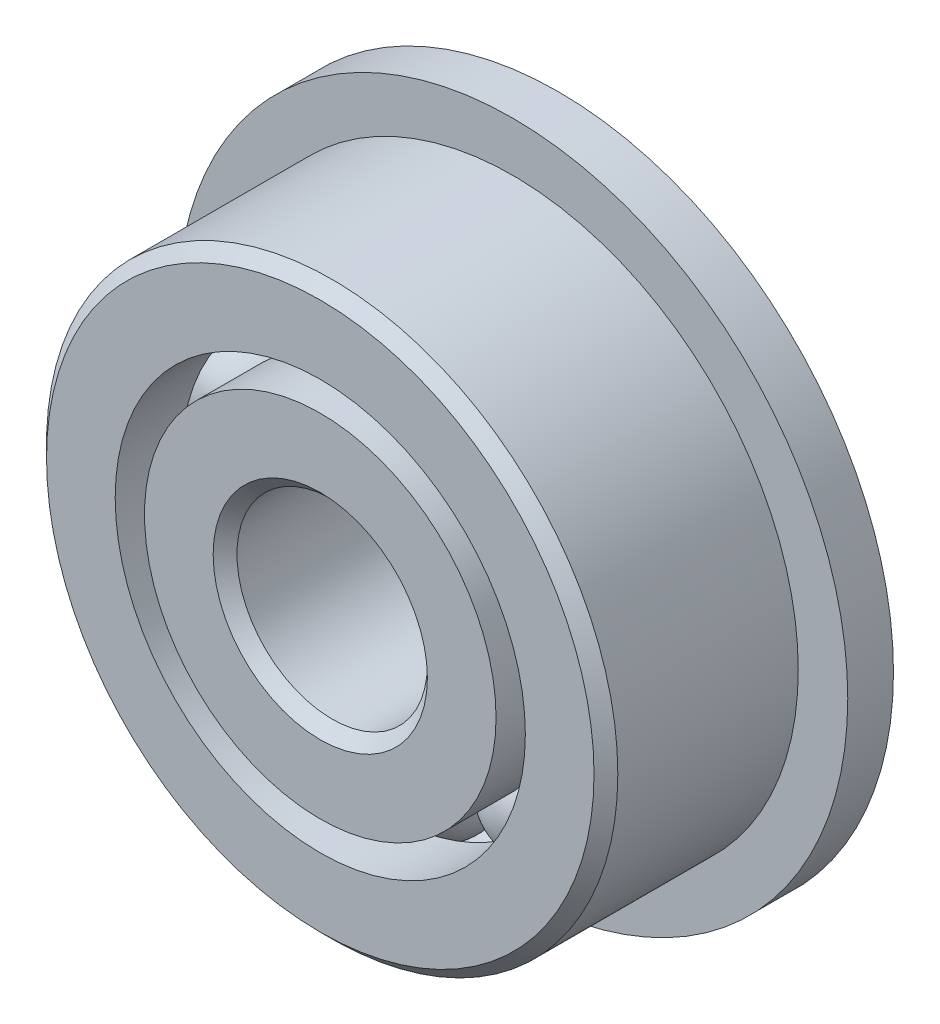
SolidWorks part; units mm, degrees
ref_plane "Front Plane" through (0, 0, 0) normal (0, 0, 1) x (1, 0, 0)
ref_plane "Top Plane" through (0, 0, 0) normal (0, 1, 0) x (1, 0, 0)
ref_plane "Right Plane" through (0, 0, 0) normal (1, 0, 0) x (0, 0, -1)
sketch "Sketch1" plane through (0, 0, 0) normal (1, 0, 0) x (0, 0, -1)
  line L0 (-1.9844, 0) -> (1.9844, 0) construction
  line L1 (0, 4.7625) -> (0, -4.7625) construction
  line L2 (1.7859, 4.7625) -> (-1.7859, 4.7625)
  line L3 (-1.7859, 4.7625) -> (-1.9844, 4.5641)
  line L4 (-1.9844, 4.5641) -> (-1.9844, 3.4192)
  line L5 (-1.9844, 3.4192) -> (-0.8819, 3.4192)
  line L6 (1.9844, 3.4192) -> (0.8819, 3.4192)
  line L7 (1.9844, 4.5641) -> (1.9844, 3.4192)
  line L8 (1.7859, 4.7625) -> (1.9844, 4.5641)
  line L9 (0, 4.7625) -> (0, 3.175) construction
  line L10 (0, 3.175) -> (0, 1.5875) construction
  arc A0 (-0.8819, 3.4192) -> (0.8819, 3.4192) centre (0, 3.175) cw
  point P14 (0, 1.5875)
  dimension "D3" = 1.7639
  dimension "D1" = 45
  dimension "Width" = 3.9688
  dimension "OD" = 9.525
  dimension "D2" = 0.1984
  dimension "Shaft Dia" = 3.175
  dimension "D4" = 0.2442
revolve "Revolve1" add sketch "Sketch1" angle 360 about L0
sketch "Sketch3" plane through (0, 0, 0) normal (1, 0, 0) x (0, 0, -1)
  line L0 (-1.9844, 2.9308) -> (-0.8819, 2.9308)
  line L1 (0, 4.7625) -> (0, -4.7625) construction
  line L2 (-1.9844, 4.5641) -> (-1.9844, 3.4192) construction
  line L3 (-1.9844, 2.9308) -> (-1.9844, 1.7859)
  line L4 (-1.7859, 4.7625) -> (-1.9844, 4.5641) construction
  line L5 (-1.9844, 1.7859) -> (-1.7859, 1.5875)
  line L6 (-1.7859, 1.5875) -> (1.7859, 1.5875)
  line L7 (1.7859, 4.7625) -> (1.7859, -4.7625) construction
  line L8 (1.7859, 1.5875) -> (1.9844, 1.7859)
  line L9 (1.9844, -4.5641) -> (1.9844, 4.5641) construction
  line L10 (1.9844, 1.7859) -> (1.9844, 2.9308)
  line L11 (1.9844, 2.9308) -> (0.8819, 2.9308)
  line L13 (1.7859, 4.7625) -> (1.9844, 4.5641) construction
  arc A0 (0.8819, 3.4192) -> (-0.8819, 3.4192) centre (0, 3.175) ccw construction
  arc A1 (0.8819, 2.9308) -> (-0.8819, 2.9308) centre (0, 3.175) cw
revolve "Revolve3" add sketch "Sketch3" angle 360 about L0
sketch "Sketch4" plane through (0, 0, 0) normal (1, 0, 0) x (0, 0, -1)
  line L0 (-0.9151, 3.175) -> (0.9151, 3.175)
  arc A2 (-0.9151, 3.175) -> (0.9151, 3.175) centre (0, 3.175) cw
  arc A3 (0.8819, 3.4192) -> (-0.8819, 3.4192) centre (0, 3.175) ccw construction
revolve "Revolve4" add sketch "Sketch4" angle 360 about L0
ref_axis "Axis1" through (0, 0, -1.9844) along (0, 0, 1)
pattern_circular "CirPattern1" count 10 every 36 about axis through (0, 0, -1.9844) along (0, 0, 1) of bodies 104
sketch "Sketch5" plane through (0, 0, 0) normal (1, 0, 0) x (0, 0, -1)
  line L0 (-1.9844, 3.4192) -> (-0.8819, 3.4192) construction
  line L1 (-1.8852, 3.4192) -> (-0.9151, 3.4192)
  line L2 (-1.8852, 3.4192) -> (-1.8852, 2.9308)
  line L3 (-1.8852, 2.9308) -> (-0.9151, 2.9308)
  line L4 (-0.9151, 3.4192) -> (-0.9151, 2.9308)
  line L5 (-1.9844, 2.9308) -> (-0.8819, 2.9308) construction
  line L6 (1.9844, 3.4192) -> (0.8819, 3.4192) construction
  line L7 (1.8852, 3.4192) -> (0.9151, 3.4192)
  line L8 (1.8852, 3.4192) -> (1.8852, 2.9308)
  line L9 (1.8852, 2.9308) -> (0.9151, 2.9308)
  line L10 (0.9151, 3.4192) -> (0.9151, 2.9308)
  line L11 (1.9844, 2.9308) -> (0.8819, 2.9308) construction
  line L12 (-1.7859, 4.7625) -> (-1.9844, 4.5641) construction
  point P18 (-1.8852, 4.6633)
revolve "Revolve5" [suppressed] add sketch "Sketch5" angle 360 about L0
sketch "Sketch6" plane through (0, 0, 0) normal (1, 0, 0) x (0, 0, -1)
  line L0 (1.9844, 0) -> (-1.9844, 0) construction
  line L1 (1.9844, 3.4192) -> (1.2224, 3.4192)
  line L2 (1.9844, 3.4192) -> (1.9844, 5.588)
  line L3 (1.9844, 5.588) -> (1.2224, 5.588)
  line L4 (1.2224, 3.4192) -> (1.2224, 5.588)
  dimension "Th" = 0.762
  dimension "Flange OD" = 11.176
revolve "Revolve6" add sketch "Sketch6" angle 360 about L0
equation "\"D2@Sketch1\" = \"Width@Sketch1\"*.05"
equation "\"D3@Sketch1\" = \"Width@Sketch1\"/2.25"
equation "\"D4@Sketch1\" = (((\"OD@Sketch1\"-\"Width@Sketch1\")/2)/3.25)/3.5"
equation "\"D2@CirPattern1\" = 360/\"Balls@CirPattern1\""
